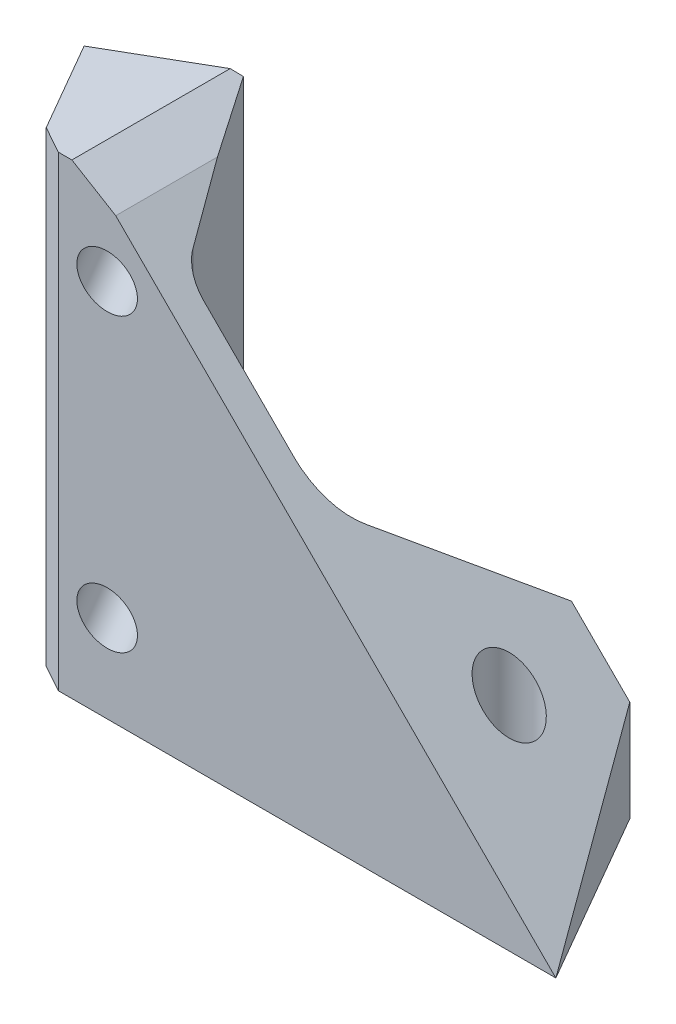
SolidWorks part; units mm, degrees
other "Markup1"
sketch "Sketch26" plane through (25.6218, 0, -129.9038) normal (-0.1134, -0.9932, -0.0259) x (0.9576, -0.1162, 0.2636)
ref_plane "Front Plane" through (0, 0, 0) normal (0, 0, 1) x (1, 0, 0)
ref_plane "Top Plane" through (0, 0, 0) normal (0, 1, 0) x (1, 0, 0)
ref_plane "Right Plane" through (0, 0, 0) normal (1, 0, 0) x (0, 0, -1)
sketch "Sketch1" plane through (0, 0, 0) normal (0, 1, 0) x (1, 0, 0)
  line L0 (0, 0) -> (150, 0)
  line L1 (0, 0) -> (75, 129.9038)
  line L2 (75, 129.9038) -> (150, 0)
  dimension "D1" = 60
  dimension "D2" = 150
  dimension "D3" = 60
sketch "Sketch2" plane through (0, 0, 0) normal (0, 1, 0) x (1, 0, 0)
  line L1 (74, 5) -> (174, 5) construction
  line L2 (74, 5) -> (74, 25) construction
  line L3 (74, 25) -> (174, 25) construction
  line L4 (174, 5) -> (174, 25) construction
  line L5 (41.3301, 61.5859) -> (91.3301, 148.1884) construction
  line L6 (91.3301, 148.1884) -> (108.6506, 138.1884) construction
  line L7 (108.6506, 138.1884) -> (58.6506, 51.5859) construction
  line L8 (58.6506, 51.5859) -> (41.3301, 61.5859) construction
  line L9 (0, 0) -> (150, 0) construction
  line L10 (108.6506, 138.1884) -> (58.6506, 51.5859)
  line L11 (58.6506, 51.5859) -> (41.3301, 61.5859)
  line L12 (41.3301, 61.5859) -> (91.3301, 148.1884)
  line L13 (91.3301, 148.1884) -> (108.6506, 138.1884)
  line L14 (74, 25) -> (174, 25)
  line L15 (174, 5) -> (174, 25)
  line L16 (74, 5) -> (174, 5)
  line L17 (74, 5) -> (74, 25)
  line L18 (0, 0) -> (75, 129.9038) construction
  dimension "D1" = 20
  dimension "D2" = 5
  dimension "D3" = 74
  dimension "D4" = 20
  dimension "D5" = 74
  dimension "D6" = 5
  dimension "D7" = 100
  dimension "D8" = 100
  dimension "D9" = 0
  dimension "D10" = 0
sketch "Sketch4" plane through (0, 0, 0) normal (0, 1, 0) x (1, 0, 0)
  line L5 (41.1191, 35.292) -> (0, 0) construction
  line L6 (0, 0) -> (53.0061, 91.8093) construction
  line L7 (68.4402, 27.9736) -> (51.1204, 17.9723) construction
  line L8 (68.4402, 27.9736) -> (58.4388, 45.2934) construction
  line L9 (58.4388, 45.2934) -> (41.1191, 35.292) construction
  line L10 (51.1204, 17.9723) -> (41.1191, 35.292) construction
  line L11 (68.4402, 27.9736) -> (41.1191, 35.292) construction
  line L12 (58.4388, 45.2934) -> (51.1204, 17.9723) construction
  line L13 (58.4388, 45.2934) -> (41.1191, 35.292)
  line L15 (0, 0) -> (131.24, 0) construction
  line L17 (51.1204, 17.9723) -> (41.1191, 35.292)
  line L18 (68.4402, 27.9736) -> (51.1204, 17.9723)
  line L19 (68.4402, 27.9736) -> (58.4388, 45.2934)
  line L20 (51.1204, 17.9723) -> (0, 0) construction
  point P0 (54.7796, 31.6328)
  dimension "D1" = 20
  dimension "D2" = 20
  dimension "D3" = 21.269
  dimension "D4" = 0
  dimension "D5" = 54.1877
  dimension "D6" = 60
  dimension "D7" = 19.37
ref_plane "Plane1" through (4.3301, 0, 2.5) normal (0.866, 0, 0.5) x (0.5, 0, -0.866)
ref_plane "Plane2" through (21.6506, 0, 12.5) normal (-0.866, 0, -0.5) x (-0.5, 0, 0.866)
ref_plane "Plane3" through (0, 0, -25) normal (0, 0, 1) x (1, 0, 0)
ref_plane "Plane4" through (0, 0, -5) normal (0, 0, 1) x (1, 0, 0)
ref_plane "Plane6" through (-5.0007, 0, -8.6599) normal (-0.5001, 0, -0.866) x (-0.866, 0, 0.5001)
ref_plane "Plane7" through (5.0007, 0, 8.6599) normal (-0.5001, 0, -0.866) x (-0.866, 0, 0.5001)
sketch "Sketch28" plane through (5.0007, 0, 8.6599) normal (-0.5001, 0, -0.866) x (-0.866, 0, 0.5001)
  line L1 (-73.2569, 0) -> (-53.2569, 0)
  line L2 (-73.2569, 0) -> (-73.2569, 80)
  line L3 (-73.2569, 80) -> (-53.2569, 80)
  line L4 (-53.2569, 0) -> (-53.2569, 80)
  dimension "D1" = 80
sketch "Sketch30" plane through (0, 0, 0) normal (0, 1, 0) x (1, 0, 0)
  line L0 (74, 5) -> (174, 5) construction
  line L1 (74, 25) -> (154, 25)
  line L2 (74, 25) -> (74, 5)
  line L3 (74, 5) -> (154, 5)
  line L4 (154, 25) -> (154, 5)
  dimension "D1" = 80
sketch "Sketch31" plane through (0, 0, 0) normal (0, 1, 0) x (1, 0, 0)
  line L7 (51.1204, 17.9723) -> (61.4986, 0)
  line L10 (78, 0) -> (150, 0)
  line L11 (61.4986, 0) -> (78, 0)
  line L14 (105.1743, 5) -> (84.5929, 5)
  line L15 (80.263, 7.4997) -> (68.4402, 27.9736)
  line L16 (68.4402, 27.9736) -> (51.1204, 17.9723)
  line L17 (68.4402, 27.9736) -> (58.4388, 45.2934) construction
  line L20 (122.6795, 30) -> (132.6795, 30)
  line L21 (132.6795, 30) -> (150, 0)
  line L22 (122.6795, 30) -> (105.1743, 5)
  line L26 (75, 129.9038) -> (150, 0) construction
  line L27 (74, 25) -> (174, 25) construction
  line L28 (0, 0) -> (150, 0) construction
  arc A2 (84.5929, 5) -> (80.263, 7.4997) centre (84.5929, 10) cw
  dimension "D1" = 5
  dimension "D2" = 5
  dimension "D3" = 125
  dimension "D4" = 10
  dimension "D5" = 72
  dimension "D6" = 5
extrude "Boss-Extrude1" add sketch "Sketch31" along normal blind 80
sketch "Sketch32" plane through (0, 0, 0) normal (0, 0, 1) x (1, 0, 0)
  line L0 (70, 80) -> (150, 0)
  line L1 (150, 0) -> (150, 80)
  line L2 (150, 80) -> (70, 80)
  dimension "D1" = 45
extrude "Cut-Extrude1" cut sketch "Sketch32" against normal blind 60
sketch "Sketch33" plane through (0, 0, 0) normal (0, 0, 1) x (1, 0, 0)
  line L0 (51.1204, 25) -> (76.1204, 0)
  line L1 (51.1204, 0) -> (51.1204, 80) construction
  line L2 (75, 0) -> (150, 0) construction
  line L3 (76.1204, 0) -> (51.1204, 0)
  line L4 (51.1204, 0) -> (51.1204, 25)
  line L5 (51.1204, 0) -> (0, 0) construction
  line L6 (0, 0) -> (150, 0) construction
  dimension "D1" = 25
  dimension "D2" = 25
extrude "Cut-Extrude2" [suppressed] cut sketch "Sketch33" against normal through all both and the other way through all
fillet "Fillet2" [suppressed] radius 10
fillet "Fillet3" radius 10 1 edges at (105.1743, 22.4128, -5)
sketch "Sketch34" plane through (5.0007, 0, 8.6599) normal (-0.5001, 0, -0.866) x (-0.866, 0, 0.5001)
  line L0 (-73.2569, 80) -> (-53.2569, 80) construction
  line L1 (-73.2569, 0) -> (-53.2569, 0) construction
  line L2 (-63.2569, 0) -> (-63.2569, 79.9187) construction
  circle A0 centre (-63.2569, 15) radius 2.3
  circle A1 centre (-63.2569, 65) radius 2.3
  point P4 (0, 0)
  point P5 (0, 0)
  point P17 (0, 0)
  dimension "D1" = 4.6
  dimension "D2" = 15
  dimension "D3" = 15
extrude "Cut-Extrude3" cut sketch "Sketch34" against normal through all both and the other way through all
ref_plane "Plane8" through (7.001, 0, 12.1238) normal (-0.5001, 0, -0.866) x (-0.866, 0, 0.5001)
sketch "Sketch35" plane through (7.001, 0, 12.1238) normal (-0.5001, 0, -0.866) x (-0.866, 0, 0.5001)
  circle A0 centre (-63.2569, 65) radius 4.5
  circle A1 centre (-63.2569, 15) radius 4.5
  dimension "D1" = 9
extrude "Cut-Extrude4" cut sketch "Sketch35" against normal through all
sketch "Sketch36" plane through (0, 0, 0) normal (0, -1, 0) x (1, 0, 0)
  line L0 (61.4986, 0) -> (150, 0) construction
  circle A0 centre (127, -15) radius 2.3
  dimension "D3" = 4.6
  dimension "D1" = 15
  dimension "D2" = 23
extrude "Cut-Extrude5" cut sketch "Sketch36" against normal through all
ref_plane "Plane9" through (0, 4, 0) normal (0, -1, 0) x (-1, 0, 0)
sketch "Sketch37" plane through (0, 4, 0) normal (0, -1, 0) x (-1, 0, 0)
  circle A0 centre (-127, 15) radius 4.5
  dimension "D1" = 9
extrude "Cut-Extrude6" cut sketch "Sketch37" against normal through all
chamfer "Chamfer1" distance 3 angle 31 1 edges at (61.4986, 40, 0) first distance on face at (56.3095, 40, -8.9861)
mirror "Mirror1" [suppressed] about plane through (0, 0, 0) normal (0, 0, 1) of bodies 151
delete or keep bodies "Body-Delete/Keep 1" [suppressed] type delete bodies bodies 151
chamfer "Chamfer3" distance 3 angle 31 1 edges at (70, 80, -12.6362) first distance on face at (64.0409, 80, -12.3027)
